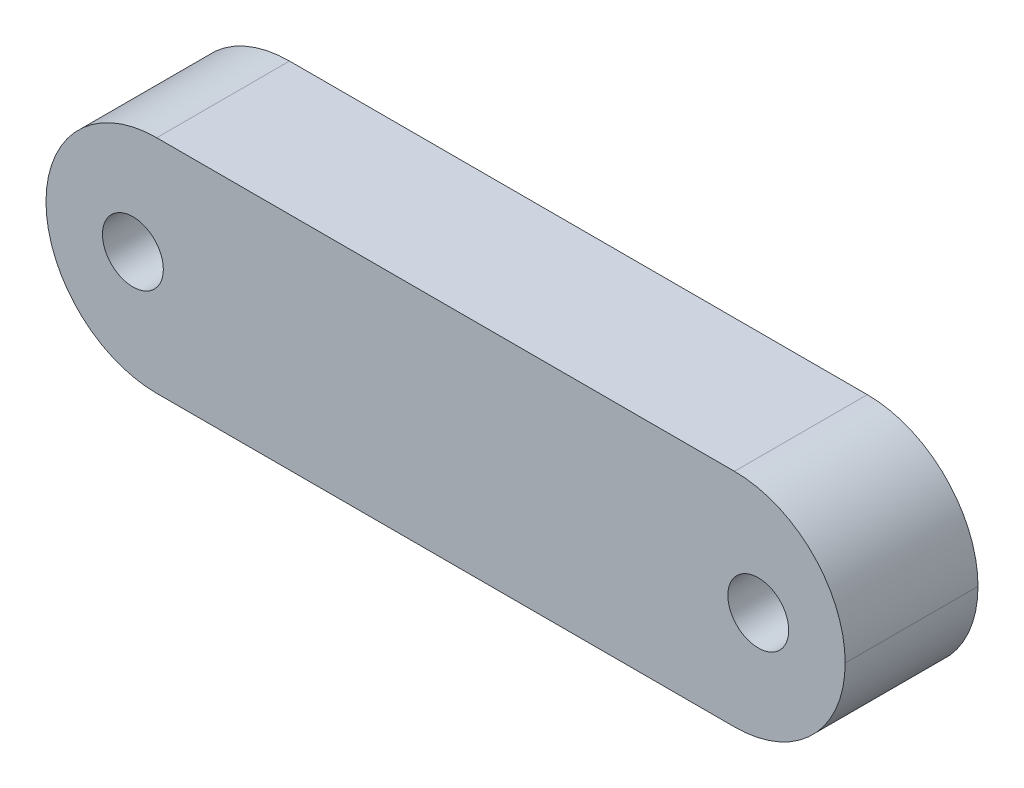
SolidWorks part; units mm, degrees
ref_plane "Front Plane" through (0, 0, 0) normal (0, 0, 1) x (1, 0, 0)
ref_plane "Top Plane" through (0, 0, 0) normal (0, 1, 0) x (1, 0, 0)
ref_plane "Right Plane" through (0, 0, 0) normal (1, 0, 0) x (0, 0, -1)
sketch "Sketch1" plane through (0, 0, 0) normal (0, 0, 1) x (1, 0, 0)
  line L0 (-28.25, 0) -> (28.25, 0) construction
  line L1 (-36.1, -10) -> (36.1, -10)
  line L2 (-36.1, -10) -> (-36.1, 10)
  line L3 (-36.1, 10) -> (36.1, 10)
  line L4 (36.1, -10) -> (36.1, 10)
  line L5 (-36.1, -10) -> (36.1, 10) construction
  line L6 (-36.1, 10) -> (36.1, -10) construction
  circle A0 centre (-28.25, 0) radius 2.75
  circle A1 centre (28.25, 0) radius 2.75
  point P0 (0, 0)
  point P9 (0, 0)
  dimension "D4" = 5.5
  dimension "D5" = 5.5
  dimension "D1" = 72.2
  dimension "D2" = 20
  dimension "D3" = 56.5
extrude "Boss-Extrude1" add sketch "Sketch1" along normal blind 12
fillet "Fillet1" radius 10 4 edges at (36.1, 10, 6) (36.1, -10, 6) (-36.1, 10, 6) (-36.1, -10, 6)
